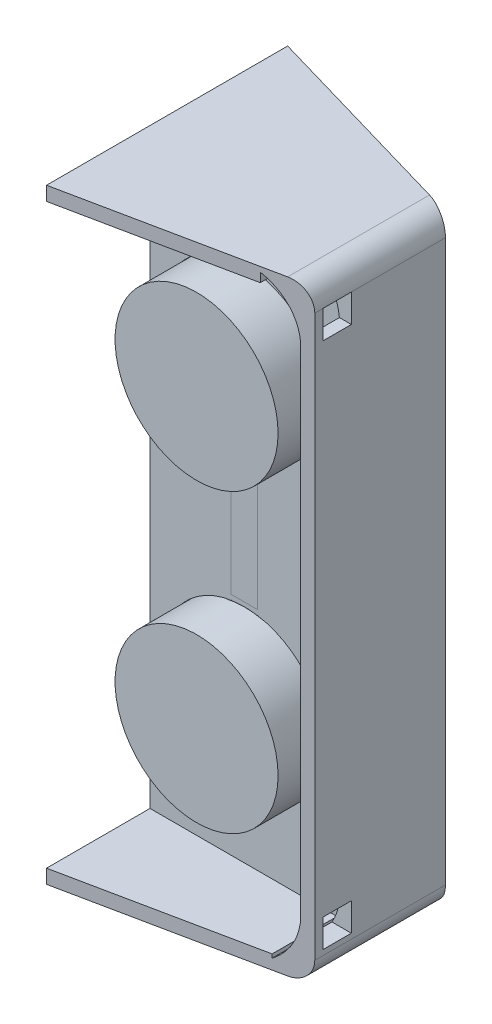
SolidWorks part; units mm, degrees
ref_plane "Front Plane" through (0, 0, 0) normal (0, 0, 1) x (1, 0, 0)
ref_plane "Top Plane" through (0, 0, 0) normal (0, 1, 0) x (1, 0, 0)
ref_plane "Right Plane" through (0, 0, 0) normal (1, 0, 0) x (0, 0, -1)
sketch "Sketch7" plane through (0, 0, 0) normal (0, 0, 1) x (1, 0, 0)
  line L68 (-111.2219, 0.1385) -> (111.0281, 0.1385) construction
  line L78 (117.3781, -142.6718) -> (187.2281, -142.6718) construction
  line L87 (111.0281, 124.6169) -> (111.0281, 92.8669) construction
  line L91 (111.0281, 124.6169) -> (111.0281, 92.8669) construction
  line L92 (117.3781, -142.6718) -> (187.2281, -142.6718) construction
  line L154 (123.7281, 130.9669) -> (187.2281, 130.9669) construction
  line L156 (123.7281, 130.9669) -> (187.2281, 130.9669) construction
  line L157 (-25.2083, 130.9669) -> (111.0281, 130.9669) construction
  line L158 (-25.2083, 130.9669) -> (111.0281, 130.9669) construction
  line L213 (117.3781, -136.3218) -> (117.3781, 124.6169)
  line L217 (117.3781, -136.3218) -> (117.3781, -142.6718)
  line L218 (117.3781, -142.6718) -> (187.2281, -142.6718)
  line L220 (212.6281, 105.5669) -> (212.6281, -117.2718)
  line L222 (187.2281, 130.9669) -> (117.3781, 130.9669)
  line L223 (117.3781, 130.9669) -> (117.3781, 124.6169)
  arc A43 (212.6281, -117.2718) -> (187.2281, -142.6718) centre (187.2281, -117.2718) cw
  arc A44 (212.6281, 105.5669) -> (187.2281, 130.9669) centre (187.2281, 105.5669) ccw
  circle A45 centre (159.9231, 61.1169) radius 36.83
  circle A46 centre (159.9231, -72.8218) radius 36.83
  circle A52 centre (198.5208, 117.0076) radius 1.905
  circle A53 centre (198.5208, -128.599) radius 1.905
  dimension "D1" = 69.85
  dimension "D4" = 25.4
  dimension "D9" = 73.66
  dimension "D3" = 38.1
extrude "Boss-Extrude1" add sketch "Sketch7" along normal blind 6.35
sketch "Sketch8" plane through (0, 0, 2.54) normal (0, 0, 1) x (1, 0, 0)
  circle A0 centre (160.02, 60.9785) radius 36.83
  circle A1 centre (160.02, -72.9602) radius 36.83
  dimension "D1" = 73.66
  dimension "D2" = 73.66
extrude "Boss-Extrude2" add sketch "Sketch8" along normal blind 25.4 and the other way blind 0.0003
sketch "Sketch9" plane through (0, 0, 0) normal (0, 0, -1) x (-1, 0, 0)
  circle A0 centre (-160.02, 60.9785) radius 34.925
  circle A1 centre (-160.02, -72.9602) radius 34.925
  dimension "D1" = 69.85
  dimension "D2" = 69.85
extrude "Cut-Extrude4" cut sketch "Sketch9" against normal blind 25.4
sketch "Sketch10" plane through (0, 0, 6.35) normal (0, 0, 1) x (1, 0, 0)
  line L0 (187.2281, 130.9669) -> (187.2281, 105.5669)
  line L1 (187.2281, 105.5669) -> (212.6281, 105.5669)
  line L2 (212.6281, -117.2718) -> (187.2281, -117.2718)
  line L3 (187.2281, -117.2718) -> (187.2281, -142.6718)
  arc A0 (212.6281, 105.5669) -> (187.2281, 130.9669) centre (187.2281, 105.5669) ccw construction
  arc A1 (187.2281, 130.9669) -> (212.6281, 105.5669) centre (187.2281, 105.5669) cw
  arc A2 (187.2281, -142.6718) -> (212.6281, -117.2718) centre (187.2281, -117.2718) ccw
extrude "Boss-Extrude3" add sketch "Sketch10" against normal blind 3.175
sketch "Sketch11" plane through (0, 0, 0) normal (0, 0, -1) x (-1, 0, 0)
  line L11 (-217.8922, -132.5118) -> (-217.8922, 120.8069)
  line L16 (-207.7322, 130.9669) -> (-187.2281, 130.9669)
  line L17 (-187.2281, -142.6718) -> (-207.7322, -142.6718)
  line L21 (-212.6281, 105.5669) -> (-212.6281, -117.2718)
  arc A2 (-187.2281, 130.9669) -> (-212.6281, 105.5669) centre (-187.2281, 105.5669) ccw
  arc A3 (-212.6281, -117.2718) -> (-187.2281, -142.6718) centre (-187.2281, -117.2718) ccw
  arc A4 (-217.8922, -132.5118) -> (-207.7322, -142.6718) centre (-207.7322, -132.5118) ccw
  arc A5 (-217.8922, 120.8069) -> (-207.7322, 130.9669) centre (-207.7322, 120.8069) cw
  dimension "D1" = 10.16
extrude "Boss-Extrude4" add sketch "Sketch11" along normal blind 38.1 and the other way blind 40.64
sketch "Sketch12" plane through (0, 0, 6.35) normal (0, 0, 1) x (1, 0, 0)
  line L15 (187.2281, 124.6169) -> (117.3781, 124.6169) construction
  line L18 (178.0511, 124.6169) -> (212.5469, 124.6169)
  line L23 (178.0511, 124.6169) -> (178.0511, -137.0862)
  line L27 (178.0511, -137.0862) -> (212.5469, -137.0862)
  line L29 (212.5469, 124.6169) -> (212.5469, -137.0862)
extrude "Cut-Extrude5" cut sketch "Sketch12" against normal blind 48.26 from offset 20.32 offset against normal yes
sketch "Sketch15" plane through (217.8922, 0, 0) normal (1, 0, 0) x (0, 0, -1)
  line L0 (38.1, 107.5959) -> (13.97, 107.5959) construction
  line L1 (13.97, 124.6169) -> (26.67, 124.6169)
  line L2 (13.97, 124.6169) -> (13.97, 107.5959)
  line L3 (13.97, 107.5959) -> (26.67, 107.5959)
  line L4 (26.67, 124.6169) -> (26.67, 107.5959)
  line L5 (0, -117.2718) -> (38.1, -117.2718) construction
  line L6 (13.97, -137.0862) -> (26.67, -137.0862)
  line L7 (13.97, -137.0862) -> (13.97, -117.2718)
  line L8 (13.97, -117.2718) -> (26.67, -117.2718)
  line L9 (26.67, -137.0862) -> (26.67, -117.2718)
  dimension "D1" = 12.7
  dimension "D2" = 12.7
sketch "Sketch16" plane through (0, 130.9669, 0) normal (0, 1, 0) x (1, 0, 0)
  line L7 (217.8922, 26.67) -> (-157.8908, 135.852)
  line L8 (217.8922, -40.64) -> (217.8922, 38.1) construction
  line L9 (-157.8908, 135.852) -> (217.8922, 135.852)
  line L10 (217.8922, 135.852) -> (217.8922, 26.67)
  line L11 (217.8922, -32.3963) -> (47.5942, -67.4767)
  line L12 (217.8922, -40.64) -> (217.8922, 38.1) construction
  line L13 (47.5942, -67.4767) -> (217.8922, -67.4767)
  line L14 (217.8922, -67.4767) -> (217.8922, -32.3963)
  point P6 (0, 0)
  point P10 (83.857, 56.6843)
  point P16 (217.8922, 26.67)
  point P18 (68.0906, -73.3891)
  point P19 (217.8922, 95.3121)
  point P20 (62.9665, -61.1701)
  point P21 (59.0248, -67.4767)
  point P22 (50.3533, -63.1409)
  point P23 (217.8922, 26.67)
  point P24 (217.8922, 26.67)
  point P25 (-74.9901, 80.7281)
  point P26 (-164.4648, 96.4946)
  point P27 (-162.8882, 114.2319)
  point P28 (47.5942, -67.4767)
  point P29 (-157.8908, 135.852)
sketch "Sketch18" plane through (0, 0, 0) normal (0, 0, -1) x (-1, 0, 0)
  line L0 (-187.2281, 130.9669) -> (-207.7322, 130.9669) construction
  line L1 (-207.7322, -142.6718) -> (-187.2281, -142.6718) construction
  line L2 (-197.4801, 130.9669) -> (-117.3781, 130.9669)
  line L3 (-197.4801, 130.9669) -> (-197.4801, 124.6169)
  line L4 (-197.4801, 124.6169) -> (-117.3781, 124.6169)
  line L5 (-117.3781, 130.9669) -> (-117.3781, 124.6169)
  line L7 (-117.3781, -136.3218) -> (-201.9067, -136.3218)
  line L8 (-117.3781, -136.3218) -> (-117.3781, -142.6718)
  line L9 (-117.3781, -142.6718) -> (-201.9067, -142.6718)
  line L10 (-201.9067, -136.3218) -> (-201.9067, -142.6718)
  point P14 (-117.3781, 124.6169)
extrude "Boss-Extrude7" add sketch "Sketch18" along normal blind 66.04 and the other way blind 55.88
extrude "Cut-Extrude7" cut sketch "Sketch16" against normal through all
sketch "Sketch19" plane through (217.8922, 0, 0) normal (1, 0, 0) x (0, 0, -1)
  line L0 (-32.3963, 120.8069) -> (26.67, 120.8069) construction
  line L1 (-15.8658, -130.1366) -> (-28.5658, -130.1366)
  line L2 (-15.8658, -130.1366) -> (-15.8658, -117.4366)
  line L3 (-15.8658, -117.4366) -> (-28.5658, -117.4366)
  line L4 (-28.5658, -130.1366) -> (-28.5658, -117.4366)
  line L5 (-15.8658, 108.1069) -> (-28.5658, 108.1069)
  line L6 (-15.8658, 108.1069) -> (-15.8658, 120.8069)
  line L7 (-15.8658, 120.8069) -> (-28.5658, 120.8069)
  line L8 (-28.5658, 108.1069) -> (-28.5658, 120.8069)
  dimension "D1" = 12.7
  dimension "D2" = 12.7
  dimension "D3" = 12.7
  dimension "D4" = 12.7
extrude "Cut-Extrude8" cut sketch "Sketch19" against normal blind 45.72
sketch "Sketch20" plane through (0, 0, 0) normal (0, 0, -1) x (-1, 0, 0)
  line L1 (-169.0247, 25.4292) -> (-150.8215, 25.4292)
  line L2 (-169.0247, 25.4292) -> (-169.0247, -37.2974)
  line L3 (-169.0247, -37.2974) -> (-150.8215, -37.2974)
  line L4 (-150.8215, 25.4292) -> (-150.8215, -37.2974)
  circle A0 centre (-159.9231, 61.1169) radius 36.83 construction
  arc A1 (-129.8, -94.0125) -> (-190.1431, -51.7695) centre (-160.02, -72.9602) ccw construction
  point P4 (-149.3891, 25.8255)
  point P7 (-149.8939, -37.5496)
  point P11 (-169.8524, 25.6506)
  point P12 (-150.8215, 25.4292)
extrude "Cut-Extrude9" cut sketch "Sketch20" against normal blind 6.35 draft 26
sketch "Sketch23" plane through (0, 0, 0) normal (0, 0, -1) x (-1, 0, 0)
  circle A0 centre (-198.5208, 117.0076) radius 1.905
  circle A1 centre (-198.5208, -128.599) radius 1.905
extrude "Cut-Extrude10" cut sketch "Sketch23" against normal through all
sketch "Sketch24" plane through (0, 0, 2.5397) normal (0, 0, -1) x (-1, 0, 0)
  line L7 (-168.1761, 25.2235) -> (-151.98, 25.2235)
  line L8 (-168.1761, 25.2235) -> (-168.1761, -37.0185)
  line L9 (-168.1761, -37.0185) -> (-151.98, -37.0185)
  line L10 (-151.98, 25.2235) -> (-151.98, -37.0185)
  arc A0 (-190.1431, 82.1692) -> (-129.8, 39.9262) centre (-159.9231, 61.1169) ccw construction
  arc A1 (-129.8, -94.0125) -> (-190.1431, -51.7695) centre (-160.02, -72.9602) ccw construction
extrude "Boss-Extrude10" add sketch "Sketch24" against normal blind 3.81
